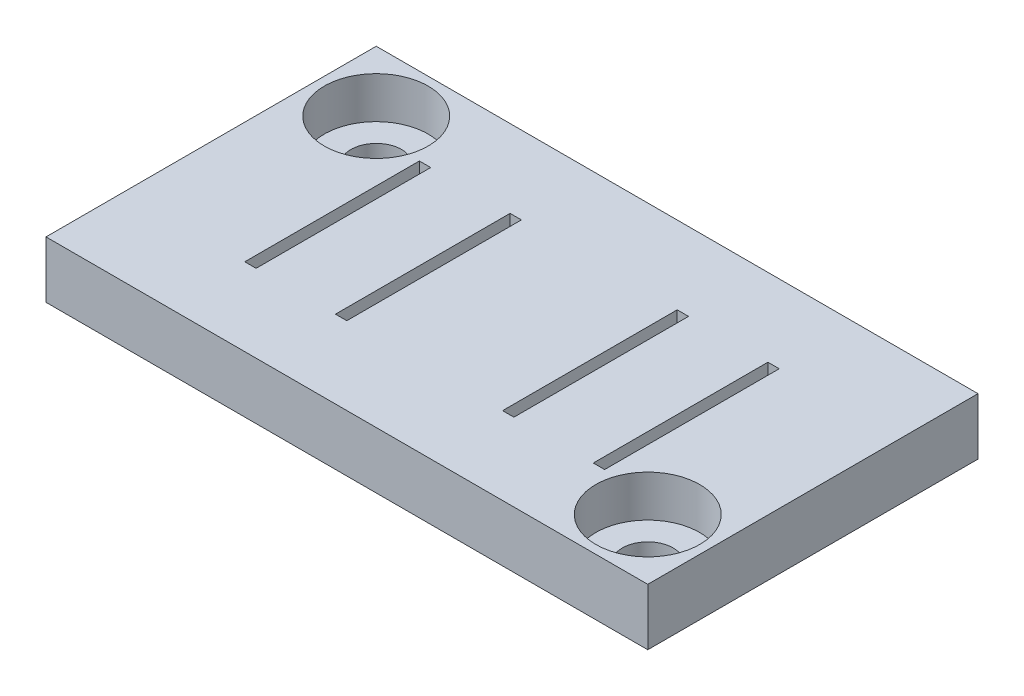
SolidWorks part; units mm, degrees
ref_plane "Front Plane" through (0, 0, 0) normal (0, 0, 1) x (1, 0, 0)
ref_plane "Top Plane" through (0, 0, 0) normal (0, 1, 0) x (1, 0, 0)
ref_plane "Right Plane" through (0, 0, 0) normal (1, 0, 0) x (0, 0, -1)
sketch "Sketch1" plane through (0, 0, 0) normal (0, 1, 0) x (1, 0, 0)
  line L1 (-20.2205, 11.0966) -> (20.2205, 11.0966)
  line L2 (-20.2205, 11.0966) -> (-20.2205, -11.0966)
  line L3 (-20.2205, -11.0966) -> (20.2205, -11.0966)
  line L4 (20.2205, 11.0966) -> (20.2205, -11.0966)
  line L5 (-20.2205, 11.0966) -> (20.2205, -11.0966) construction
  line L6 (-20.2205, -11.0966) -> (20.2205, 11.0966) construction
  point P0 (0, 0)
  dimension "D1" = 40.4409
  dimension "D2" = 22.1932
extrude "Boss-Extrude1" add sketch "Sketch1" along normal blind 3.81
sketch "Sketch3" plane through (0, 3.81, 0) normal (0, 1, 0) x (1, 0, 0)
  line L0 (-12.0925, 7.0326) -> (-20.2205, 7.0326) construction
  line L1 (-20.2205, 11.0966) -> (-12.0925, 11.0966)
  line L2 (-20.2205, 11.0966) -> (-20.2205, 2.9686)
  line L3 (-20.2205, 2.9686) -> (-12.0925, 2.9686)
  line L4 (-12.0925, 11.0966) -> (-12.0925, 2.9686)
  line L5 (20.2205, -11.0966) -> (12.0925, -11.0966)
  line L6 (20.2205, -11.0966) -> (20.2205, -2.9686)
  line L7 (20.2205, -2.9686) -> (12.0925, -2.9686)
  line L8 (12.0925, -11.0966) -> (12.0925, -2.9686)
  line L9 (12.0925, -7.0326) -> (20.2205, -7.0326) construction
  circle A0 centre (-16.1565, 7.0326) radius 1.7018
  circle A1 centre (16.1565, -7.0326) radius 1.7018
  circle A2 centre (-16.1565, 7.0326) radius 3.4925
  circle A3 centre (16.1565, -7.0326) radius 3.4925
  dimension "D5" = 6.985
  dimension "D6" = 6.985
  dimension "D1" = 8.128
  dimension "D2" = 8.128
  dimension "D3" = 8.128
  dimension "D4" = 8.128
extrude "Cut-Extrude3" cut sketch "Sketch3" against normal blind 2.794 contours A2 | A3
extrude "Cut-Extrude4" cut sketch "Sketch3<4>" against normal through all contours A0 | A1
sketch "Sketch3<4>" plane through (0, 3.81, 0) normal (0, 1, 0) x (1, 0, 0) same geometry as "Sketch3"
sketch "Sketch7" plane through (0, 3.81, 0) normal (0, 1, 0) x (1, 0, 0)
  line L0 (-20.2205, 11.0966) -> (-12.0925, 11.0966) construction
  line L1 (20.2205, 11.0966) -> (-20.2205, 11.0966) construction
  line L2 (-12.0925, 11.0966) -> (-12.0925, 2.9686) construction
  line L3 (-12.0925, 2.9686) -> (-20.2205, 2.9686) construction
  line L4 (-20.2205, 11.0966) -> (-20.2205, -11.0966) construction
  line L5 (20.2205, -11.0966) -> (12.0925, -11.0966) construction
  line L6 (-20.2205, -11.0966) -> (20.2205, -11.0966) construction
  line L7 (12.0925, -11.0966) -> (12.0925, -2.9686) construction
  line L8 (12.0925, -2.9686) -> (20.2205, -2.9686) construction
  line L9 (20.2205, -11.0966) -> (20.2205, 11.0966) construction
  line L10 (-12.0925, 2.9686) -> (12.0925, 2.9686) construction
  line L11 (12.0925, 2.9686) -> (12.0925, -2.9686) construction
  line L12 (12.0925, -2.9686) -> (-12.0925, -2.9686) construction
  line L13 (-12.0925, -2.9686) -> (-12.0925, 2.9686) construction
  line L14 (-12.0925, 0) -> (-11.7115, 0) construction
  line L15 (-11.7115, 0) -> (-5.6155, 0) construction
  line L16 (-12.0925, -5.8674) -> (-11.3305, -5.8674)
  line L17 (-12.0925, -5.8674) -> (-12.0925, 5.8674)
  line L18 (-12.0925, 5.8674) -> (-11.3305, 5.8674)
  line L19 (-11.3305, -5.8674) -> (-11.3305, 5.8674)
  line L20 (-12.0925, -5.8674) -> (-11.3305, 5.8674) construction
  line L21 (-12.0925, 5.8674) -> (-11.3305, -5.8674) construction
  line L22 (12.0925, 0) -> (11.7115, 0) construction
  line L23 (-5.9965, -5.8674) -> (-5.2345, -5.8674)
  line L24 (-5.9965, -5.8674) -> (-5.9965, 5.8674)
  line L25 (-5.9965, 5.8674) -> (-5.2345, 5.8674)
  line L26 (-5.2345, -5.8674) -> (-5.2345, 5.8674)
  line L27 (-5.9965, -5.8674) -> (-5.2345, 5.8674) construction
  line L28 (-5.9965, 5.8674) -> (-5.2345, -5.8674) construction
  line L29 (11.7115, 0) -> (5.6155, 0) construction
  line L30 (11.3305, 5.8674) -> (12.0925, 5.8674)
  line L31 (11.3305, 5.8674) -> (11.3305, -5.8674)
  line L32 (11.3305, -5.8674) -> (12.0925, -5.8674)
  line L33 (12.0925, 5.8674) -> (12.0925, -5.8674)
  line L34 (11.3305, 5.8674) -> (12.0925, -5.8674) construction
  line L35 (11.3305, -5.8674) -> (12.0925, 5.8674) construction
  line L37 (5.2345, 5.8674) -> (5.9965, 5.8674)
  line L38 (5.2345, 5.8674) -> (5.2345, -5.8674)
  line L39 (5.2345, -5.8674) -> (5.9965, -5.8674)
  line L40 (5.9965, 5.8674) -> (5.9965, -5.8674)
  line L41 (5.2345, 5.8674) -> (5.9965, -5.8674) construction
  line L42 (5.2345, -5.8674) -> (5.9965, 5.8674) construction
  dimension "D1" = 8.128
  dimension "D2" = 8.128
  dimension "D3" = 8.128
  dimension "D4" = 8.128
  dimension "D5" = 0.381
  dimension "D6" = 0.762
  dimension "D7" = 11.7348
  dimension "D8" = 6.096
  dimension "D9" = 0.762
  dimension "D10" = 0.381
  dimension "D11" = 6.096
  dimension "D12" = 0.762
extrude "Cut-Extrude5" cut sketch "Sketch7" against normal through all
